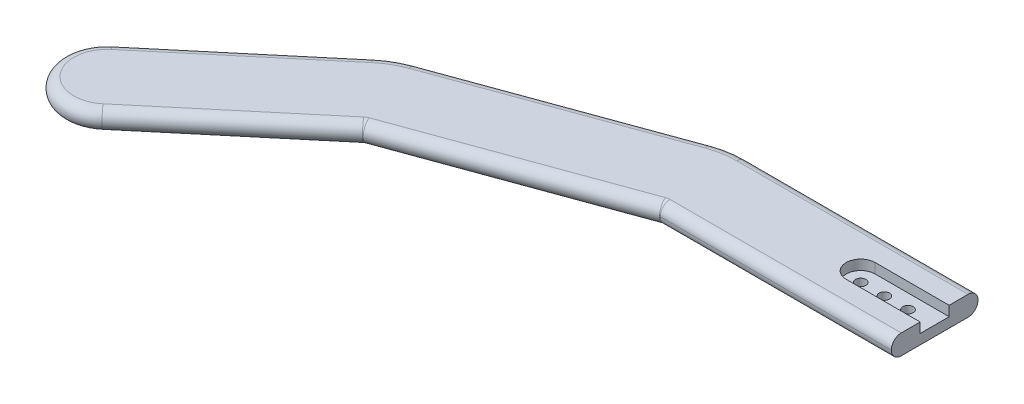
SolidWorks part; units mm, degrees
ref_plane "Front Plane" through (0, 0, 0) normal (0, 0, 1) x (1, 0, 0)
ref_plane "Top Plane" through (0, 0, 0) normal (0, 1, 0) x (1, 0, 0)
ref_plane "Right Plane" through (0, 0, 0) normal (1, 0, 0) x (0, 0, -1)
sketch "Sketch1" plane through (0, 0, 0) normal (0, 1, 0) x (1, 0, 0)
  line L1 (0, 0) -> (-25.4, 0)
  line L2 (0, 0) -> (0, -9.525)
  line L3 (0, -9.525) -> (-25.4, -9.525)
  line L4 (-25.4, 0) -> (-25.4, -9.525)
  dimension "D1" = 9.525
  dimension "D2" = 25.4
extrude "Boss-Extrude1" add sketch "Sketch1" along normal blind 1.0922
sketch "Sketch2" plane through (0, 1.0922, 0) normal (0, 1, 0) x (1, 0, 0)
  line L0 (-8.128, -4.7625) -> (0, -4.7625) construction
  line L1 (0, -9.525) -> (0, 0) construction
  line L2 (-8.128, -3.1686) -> (0, -3.1686)
  line L3 (-8.128, -6.3563) -> (0, -6.3563)
  line L4 (0, -6.3563) -> (0, -9.525)
  line L5 (0, -9.525) -> (-25.4, -9.525)
  line L6 (-25.4, -9.525) -> (-25.4, 0)
  line L7 (-25.4, 0) -> (0, 0)
  line L8 (0, 0) -> (0, -3.1686)
  arc A0 (-8.128, -3.1686) -> (-8.128, -6.3563) centre (-8.128, -4.7625) ccw
  dimension "D1" = 8.128
  dimension "D2" = 3.1877
extrude "Boss-Extrude2" add sketch "Sketch2" along normal blind 1.0922
fillet "Fillet1" radius 1.0922 4 edges at (-12.7, 0, 0) (-12.7, 2.1844, 0) (-12.7, 0, 9.525) (-12.7, 2.1844, 9.525)
sketch "Sketch3" plane through (0, 1.0922, 0) normal (0, 1, 0) x (1, 0, 0)
  line L0 (-8.128, -4.7625) -> (-5.528, -4.7625) construction
  line L1 (-5.528, -4.7625) -> (-2.928, -4.7625) construction
  circle A0 centre (-8.128, -4.7625) radius 0.575
  circle A1 centre (-5.528, -4.7625) radius 0.575
  circle A2 centre (-2.928, -4.7625) radius 0.575
  arc A4 (-8.128, -3.1686) -> (-8.128, -6.3563) centre (-8.128, -4.7625) ccw construction
  dimension "D2" = 1.15
  dimension "D1" = 2.6
extrude "Cut-Extrude1" cut sketch "Sketch3" against normal through all
sketch "Sketch6" plane through (-25.4, 0, 0) normal (-1, 0, 0) x (0, 0, 1)
  line L0 (8.4328, 2.1844) -> (9.7028, 2.1844) construction
  line L1 (8.4328, 2.1844) -> (8.4328, 0) construction
  line L2 (9.7028, 2.1844) -> (9.7028, 0)
  line L3 (8.4328, 0) -> (9.7028, 0) construction
  dimension "D1" = 1.27
ref_axis "Axis1" through (-25.4, 2.1844, 9.7028) along (0, -1, 0)
sketch "Sketch5" plane through (-25.4, 0, 0) normal (-1, 0, 0) x (0, 0, 1)
  line L2 (1.0922, 0) -> (8.4328, 0)
  line L3 (8.4328, 2.1844) -> (1.0922, 2.1844)
  line L4 (1.0922, 0) -> (8.4328, 0)
  line L5 (8.4328, 2.1844) -> (1.0922, 2.1844)
  arc A4 (1.0922, 2.1844) -> (0, 1.0922) centre (1.0922, 1.0922) ccw
  arc A5 (0, 1.0922) -> (1.0922, 0) centre (1.0922, 1.0922) ccw
  arc A6 (8.4328, 0) -> (9.525, 1.0922) centre (8.4328, 1.0922) ccw
  arc A7 (9.525, 1.0922) -> (8.4328, 2.1844) centre (8.4328, 1.0922) ccw
  arc A8 (1.0922, 2.1844) -> (0, 1.0922) centre (1.0922, 1.0922) ccw
  arc A9 (0, 1.0922) -> (1.0922, 0) centre (1.0922, 1.0922) ccw
  arc A10 (8.4328, 0) -> (9.525, 1.0922) centre (8.4328, 1.0922) ccw
  arc A11 (9.525, 1.0922) -> (8.4328, 2.1844) centre (8.4328, 1.0922) ccw
  dimension "D1" = 0
revolve "Revolve1" add sketch "Sketch5" angle 20 about axis through (-25.4, 2.1844, 9.7028) along (0, -1, 0) reverse direction yes
sketch "Sketch7" plane through (-25.5472, 0, 9.2984) normal (-0.9397, 0, 0.342) x (0.342, 0, 0.9397)
  line L2 (-8.1803, 0) -> (-0.8397, 0)
  line L3 (-0.8397, 2.1844) -> (-8.1803, 2.1844)
  line L4 (-8.1803, 0) -> (-0.8397, 0)
  line L5 (-0.8397, 2.1844) -> (-8.1803, 2.1844)
  arc A2 (-8.1803, 2.1844) -> (-8.1803, 0) centre (-8.1803, 1.0922) ccw
  arc A3 (-0.8397, 0) -> (-0.8397, 2.1844) centre (-0.8397, 1.0922) ccw
  arc A4 (-8.1803, 2.1844) -> (-8.1803, 0) centre (-8.1803, 1.0922) ccw
  arc A5 (-0.8397, 0) -> (-0.8397, 2.1844) centre (-0.8397, 1.0922) ccw
  dimension "D1" = 0
extrude "Boss-Extrude3" add sketch "Sketch7" along normal blind 25.4
sketch "Sketch8" plane through (-49.4154, 0, 17.9857) normal (-0.9397, 0, 0.342) x (0.342, 0, 0.9397)
  line L0 (-0.8397, 2.1844) -> (-0.8397, 0) construction
  line L1 (-0.8397, 2.1844) -> (0.4303, 2.1844) construction
  line L2 (-0.8397, 0) -> (0.4303, 0) construction
  line L3 (0.4303, 2.1844) -> (0.4303, 0)
  dimension "D1" = 1.27
ref_axis "Axis2" through (-49.2682, 2.1844, 18.3901) along (0, -1, 0)
sketch "Sketch9" plane through (-49.4154, 0, 17.9857) normal (-0.9397, 0, 0.342) x (0.342, 0, 0.9397)
  line L2 (-8.1803, 0) -> (-0.8397, 0)
  line L3 (-0.8397, 2.1844) -> (-8.1803, 2.1844)
  line L4 (-8.1803, 0) -> (-0.8397, 0)
  line L5 (-0.8397, 2.1844) -> (-8.1803, 2.1844)
  arc A2 (-8.1803, 2.1844) -> (-8.1803, 0) centre (-8.1803, 1.0922) ccw
  arc A3 (-0.8397, 0) -> (-0.8397, 2.1844) centre (-0.8397, 1.0922) ccw
  arc A4 (-8.1803, 2.1844) -> (-8.1803, 0) centre (-8.1803, 1.0922) ccw
  arc A5 (-0.8397, 0) -> (-0.8397, 2.1844) centre (-0.8397, 1.0922) ccw
  dimension "D1" = 0
revolve "Revolve2" add sketch "Sketch9" angle 20 about axis through (-49.2682, 2.1844, 18.3901) along (0, -1, 0) reverse direction yes
sketch "Sketch10" plane through (-37.9671, 0, 31.8582) normal (-0.766, 0, 0.6428) x (0.6428, 0, 0.766)
  line L2 (-26.1919, 0) -> (-18.8513, 0)
  line L3 (-18.8513, 2.1844) -> (-26.1919, 2.1844)
  line L4 (-26.1919, 0) -> (-18.8513, 0)
  line L5 (-18.8513, 2.1844) -> (-26.1919, 2.1844)
  arc A2 (-26.1919, 2.1844) -> (-26.1919, 0) centre (-26.1919, 1.0922) ccw
  arc A3 (-18.8513, 0) -> (-18.8513, 2.1844) centre (-18.8513, 1.0922) ccw
  arc A4 (-26.1919, 2.1844) -> (-26.1919, 0) centre (-26.1919, 1.0922) ccw
  arc A5 (-18.8513, 0) -> (-18.8513, 2.1844) centre (-18.8513, 1.0922) ccw
  dimension "D1" = 0
extrude "Boss-Extrude4" add sketch "Sketch10" along normal blind 20.32
sketch "Sketch11" plane through (-53.5331, 0, 44.9196) normal (-0.766, 0, 0.6428) x (0.6428, 0, 0.766)
  line L0 (-22.5216, 2.1844) -> (-22.5216, 0)
  line L2 (-26.1919, 0) -> (-18.8513, 0)
  line L3 (-18.8513, 2.1844) -> (-26.1919, 2.1844)
  line L4 (-26.1919, 0) -> (-18.8513, 0)
  line L5 (-18.8513, 2.1844) -> (-26.1919, 2.1844)
  arc A2 (-26.1919, 2.1844) -> (-26.1919, 0) centre (-26.1919, 1.0922) ccw
  arc A3 (-18.8513, 0) -> (-18.8513, 2.1844) centre (-18.8513, 1.0922) ccw
  arc A4 (-26.1919, 2.1844) -> (-26.1919, 0) centre (-26.1919, 1.0922) ccw
  arc A5 (-18.8513, 0) -> (-18.8513, 2.1844) centre (-18.8513, 1.0922) ccw
  dimension "D1" = 0
revolve "Revolve3" add sketch "Sketch11" angle 180 about L0 region at (-66.5503, 1.0922, 29.4065)
